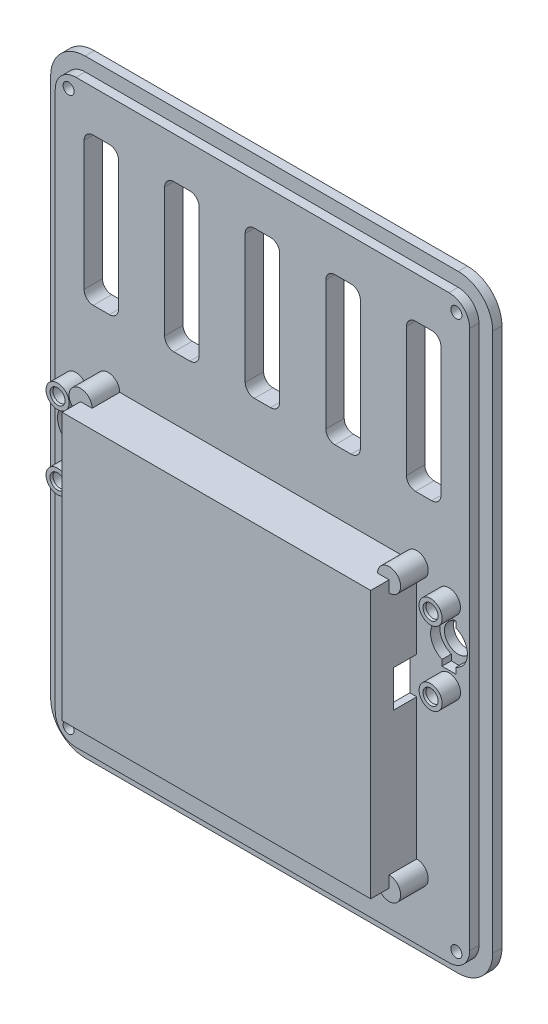
SolidWorks part; units mm, degrees
ref_plane "Front Plane" through (0, 0, 0) normal (0, 0, 1) x (1, 0, 0)
ref_plane "Top Plane" through (0, 0, 0) normal (0, 1, 0) x (1, 0, 0)
ref_plane "Right Plane" through (0, 0, 0) normal (1, 0, 0) x (0, 0, -1)
sketch "Sketch2" plane through (0, 0, 0) normal (0, 0, 1) x (1, 0, 0)
  line L20 (45, -58.5) -> (45, 58.5)
  line L21 (-40.5, -63) -> (40.5, -63)
  line L22 (-45, 58.5) -> (-45, -58.5)
  line L23 (40.5, 63) -> (-40.5, 63)
  line L24 (45, -58.5) -> (45, 58.5)
  line L25 (-40.5, -63) -> (40.5, -63)
  line L26 (-45, 58.5) -> (-45, -58.5)
  line L27 (40.5, 63) -> (-40.5, 63)
  arc A24 (40.5, -63) -> (45, -58.5) centre (40.5, -58.5) ccw
  arc A25 (-45, -58.5) -> (-40.5, -63) centre (-40.5, -58.5) ccw
  arc A26 (-40.5, 63) -> (-45, 58.5) centre (-40.5, 58.5) ccw
  arc A27 (45, 58.5) -> (40.5, 63) centre (40.5, 58.5) ccw
  arc A28 (40.5, -63) -> (45, -58.5) centre (40.5, -58.5) ccw
  arc A29 (-45, -58.5) -> (-40.5, -63) centre (-40.5, -58.5) ccw
  arc A30 (-40.5, 63) -> (-45, 58.5) centre (-40.5, 58.5) ccw
  arc A31 (45, 58.5) -> (40.5, 63) centre (40.5, 58.5) ccw
  dimension "D1" = 3
extrude "Boss-Extrude1" add sketch "Sketch2" along normal blind 2
sketch "Sketch3" plane through (0, 0, 0) normal (0, 0, -1) x (-1, 0, 0)
  line L8 (-40.5, -66) -> (40.5, -66)
  line L9 (48, -58.5) -> (48, 58.5)
  line L10 (40.5, 66) -> (-40.5, 66)
  line L11 (-48, 58.5) -> (-48, -58.5)
  line L12 (-40.5, -66) -> (40.5, -66)
  line L13 (48, -58.5) -> (48, 58.5)
  line L14 (40.5, 66) -> (-40.5, 66)
  line L15 (-48, 58.5) -> (-48, -58.5)
  arc A8 (-48, -58.5) -> (-40.5, -66) centre (-40.5, -58.5) ccw
  arc A9 (40.5, -66) -> (48, -58.5) centre (40.5, -58.5) ccw
  arc A10 (48, 58.5) -> (40.5, 66) centre (40.5, 58.5) ccw
  arc A11 (-40.5, 66) -> (-48, 58.5) centre (-40.5, 58.5) ccw
  arc A12 (-48, -58.5) -> (-40.5, -66) centre (-40.5, -58.5) ccw
  arc A13 (40.5, -66) -> (48, -58.5) centre (40.5, -58.5) ccw
  arc A14 (48, 58.5) -> (40.5, 66) centre (40.5, 58.5) ccw
  arc A15 (-40.5, 66) -> (-48, 58.5) centre (-40.5, 58.5) ccw
  dimension "D1" = 3
extrude "Boss-Extrude2" add sketch "Sketch3" along normal blind 2
sketch "Sketch5" plane through (0, 0, -2) normal (0, 0, -1) x (-1, 0, 0)
  line L0 (-48, 38) -> (48, 38) construction
  line L1 (-36.75, 22) -> (-33.25, 22)
  line L2 (-38.75, 24) -> (-38.75, 52)
  line L3 (-36.75, 54) -> (-33.25, 54)
  line L4 (-31.25, 24) -> (-31.25, 52)
  line L5 (-38.75, 22) -> (-31.25, 54) construction
  line L6 (-38.75, 54) -> (-31.25, 22) construction
  line L7 (-48, 58.5) -> (-48, -58.5) construction
  line L8 (48, -58.5) -> (48, 58.5) construction
  line L9 (40.5, 66) -> (-40.5, 66) construction
  line L10 (-21.25, 24) -> (-21.25, 52)
  line L11 (-13.75, 24) -> (-13.75, 52)
  line L12 (-19.25, 54) -> (-15.75, 54)
  line L13 (-19.25, 22) -> (-15.75, 22)
  line L14 (-21.25, 54) -> (-13.75, 22) construction
  line L15 (-21.25, 22) -> (-13.75, 54) construction
  line L16 (-3.75, 24) -> (-3.75, 52)
  line L17 (3.75, 24) -> (3.75, 52)
  line L18 (-1.75, 54) -> (1.75, 54)
  line L19 (-1.75, 22) -> (1.75, 22)
  line L20 (-3.75, 54) -> (3.75, 22) construction
  line L21 (-3.75, 22) -> (3.75, 54) construction
  line L22 (13.75, 24) -> (13.75, 52)
  line L23 (21.25, 24) -> (21.25, 52)
  line L24 (15.75, 54) -> (19.25, 54)
  line L25 (15.75, 22) -> (19.25, 22)
  line L26 (13.75, 54) -> (21.25, 22) construction
  line L27 (13.75, 22) -> (21.25, 54) construction
  line L28 (31.25, 24) -> (31.25, 52)
  line L29 (38.75, 24) -> (38.75, 52)
  line L30 (33.25, 54) -> (36.75, 54)
  line L31 (33.25, 22) -> (36.75, 22)
  line L32 (31.25, 54) -> (38.75, 22) construction
  line L33 (31.25, 22) -> (38.75, 54) construction
  line L34 (-3.5, 66) -> (-3.5, 34) construction
  arc A0 (31.25, 52) -> (33.25, 54) centre (33.25, 52) cw
  arc A1 (38.75, 52) -> (36.75, 54) centre (36.75, 52) ccw
  arc A2 (38.75, 24) -> (36.75, 22) centre (36.75, 24) cw
  arc A3 (31.25, 24) -> (33.25, 22) centre (33.25, 24) ccw
  arc A4 (13.75, 24) -> (15.75, 22) centre (15.75, 24) ccw
  arc A5 (21.25, 24) -> (19.25, 22) centre (19.25, 24) cw
  arc A6 (21.25, 52) -> (19.25, 54) centre (19.25, 52) ccw
  arc A7 (13.75, 52) -> (15.75, 54) centre (15.75, 52) cw
  arc A8 (3.75, 24) -> (1.75, 22) centre (1.75, 24) cw
  arc A9 (-3.75, 24) -> (-1.75, 22) centre (-1.75, 24) ccw
  arc A10 (3.75, 52) -> (1.75, 54) centre (1.75, 52) ccw
  arc A11 (-3.75, 52) -> (-1.75, 54) centre (-1.75, 52) cw
  arc A12 (-21.25, 24) -> (-19.25, 22) centre (-19.25, 24) ccw
  arc A13 (-13.75, 24) -> (-15.75, 22) centre (-15.75, 24) cw
  arc A14 (-13.75, 52) -> (-15.75, 54) centre (-15.75, 52) ccw
  arc A15 (-21.25, 52) -> (-19.25, 54) centre (-19.25, 52) cw
  arc A16 (-33.25, 22) -> (-31.25, 24) centre (-33.25, 24) ccw
  arc A17 (-36.75, 22) -> (-38.75, 24) centre (-36.75, 24) cw
  arc A18 (-33.25, 54) -> (-31.25, 52) centre (-33.25, 52) cw
  arc A19 (-38.75, 52) -> (-36.75, 54) centre (-36.75, 52) cw
  point P0 (-35, 38)
  point P13 (-17.5, 38)
  point P19 (0, 38)
  point P24 (17.5, 38)
  point P29 (35, 38)
  dimension "D6" = 2
  dimension "D1" = 7.5
  dimension "D2" = 32
  dimension "D3" = 28
  dimension "D5" = 10
  dimension "D4" = 5
extrude "Cut-Extrude1" cut sketch "Sketch5" against normal through all
hole_wizard "CBORE for M2 Pan Head Machine Screw1" positions "Sketch7" profile "Sketch6" counterbore size "M2" standard "ANSI Metric" end condition through all
sketch "Sketch7" plane through (0, 0, -2) normal (0, 0, -1) x (-1, 0, 0)
  point P0 (-42.1, 60.1)
  point P3 (42.1, 60.1)
  point P6 (-42.1, -60.1)
  point P9 (42.1, -60.1)
sketch "Sketch6" plane through (42.1, 60.1, -2) normal (1, 0, 0) x (0, 1, 0)
  line L0 (0, 0) -> (0, 4)
  line L1 (0, 4) -> (1.2, 4)
  line L3 (1.2, 4) -> (1.2, 1.6)
  line L4 (1.2, 1.6) -> (2.5, 1.6)
  line L5 (2.5, 1.6) -> (2.5, 0)
  line L7 (2.5, 0) -> (0, 0)
  line L11 (0, -6.35) -> (0, 107.95) construction
  dimension "Thru Hole Dia." = 2.4
  dimension "Thru Hole Depth" = 4
  dimension "C'Bore Dia." = 5
  dimension "C'Bore Depth" = 1.6
sketch "Sketch8" plane through (0, 0, -2) normal (0, 0, -1) x (-1, 0, 0)
  line L0 (0, 66) -> (0, -66) construction
  line L1 (-32, 7) -> (32, 7)
  line L2 (-32, 7) -> (-32, -48)
  line L3 (-32, -48) -> (32, -48)
  line L4 (32, 7) -> (32, -48)
  line L5 (-32, 7) -> (32, -48) construction
  line L6 (-32, -48) -> (32, 7) construction
  line L7 (40.5, 66) -> (-40.5, 66) construction
  line L8 (-40.5, -66) -> (40.5, -66) construction
  line L9 (-33.5, 8.5) -> (33.5, 8.5)
  line L10 (33.5, 8.5) -> (33.5, -49.5)
  line L11 (-33.5, -49.5) -> (33.5, -49.5)
  line L12 (-33.5, 8.5) -> (-33.5, -49.5)
  point P0 (0, -20.5)
  dimension "D1" = 18
  dimension "D2" = 55
  dimension "D3" = 64
  dimension "D4" = 1.5
extrude "Boss-Extrude3" add sketch "Sketch8<3>" against normal blind 10 from surface contours L9 L10 L11 L12 starting at face at (40.9, 60.1, 2)
sketch "Sketch8<3>" plane through (0, 0, -2) normal (0, 0, -1) x (-1, 0, 0) same geometry as "Sketch8"
extrude "Cut-Extrude2" cut sketch "Sketch8" against normal blind 12 contours L1 L4 L3 L2
sketch "Sketch9" plane through (0, 0, -2) normal (0, 0, -1) x (-1, 0, 0)
  line L18 (-36, -52) -> (36, -52)
  line L19 (36, -52) -> (36, 11)
  line L20 (-36, 11) -> (-36, -52)
  line L21 (36, 11) -> (-36, 11)
  line L22 (-36, -52) -> (36, -52)
  line L23 (36, -52) -> (36, 11)
  line L24 (-36, 11) -> (-36, -52)
  line L25 (36, 11) -> (-36, 11)
  dimension "D1" = 4
extrude "Cut-Extrude3" cut sketch "Sketch9" against normal blind 2
sketch "Sketch10" plane through (0, 0, 2) normal (0, 0, 1) x (1, 0, 0)
  line L0 (32, 7) -> (31.5, 7)
  line L1 (-32, 7) -> (-32, 6.5)
  line L2 (-32, -48) -> (-31.5, -48)
  line L3 (32, -48) -> (32, -47.5)
  line L4 (32, 6.5) -> (32, 7)
  line L5 (-31.5, 7) -> (-32, 7)
  line L6 (-32, -47.5) -> (-32, -48)
  line L7 (31.5, -48) -> (32, -48)
  arc A0 (32, 6.5) -> (31.5, 7) centre (33.5, 8.5) ccw
  arc A1 (-31.5, 7) -> (-32, 6.5) centre (-33.5, 8.5) ccw
  arc A2 (-32, -47.5) -> (-31.5, -48) centre (-33.5, -49.5) ccw
  arc A3 (31.5, -48) -> (32, -47.5) centre (33.5, -49.5) ccw
  dimension "D1" = 5
extrude "Boss-Extrude4" add sketch "Sketch10" along normal blind 6
hole_wizard "CSK for M2 Flat Head Machine Screw2" positions "Sketch14" profile "Sketch13" countersink size "M2" standard "ANSI Metric"
sketch "Sketch14" plane through (0, 0, 0) normal (0, 0, -1) x (-1, 0, 0)
  point P0 (-33.5, 8.5)
  point P3 (33.5, 8.5)
  point P6 (-33.5, -49.5)
  point P9 (33.5, -49.5)
sketch "Sketch13" plane through (33.5, 8.5, 0) normal (1, 0, 0) x (0, 1, 0)
  line L0 (0, 0) -> (0, 6.9013)
  line L1 (0, 6.9013) -> (1.5, 6)
  line L2 (1.5, 6) -> (1.5, 0.5038)
  line L3 (1.5, 0.5038) -> (1.635, 0)
  line L5 (1.635, 0) -> (0, 0)
  line L6 (-1.5, 0.5038) -> (-1.635, 0) construction
  line L10 (0, 6.9013) -> (-1.5, 6) construction
  line L11 (0, -6.35) -> (0, 107.95) construction
  dimension "Hole Dia." = 3
  dimension "Hole Depth" = 6
  dimension "Near C'Sink Dia." = 3.27
  dimension "Near C'Sink Angle" = 30
  dimension "Drill Angle" = 118
sketch "Sketch15" plane through (33.5, 0, 0) normal (1, 0, 0) x (0, 0, -1)
  line L1 (-7, -8.5) -> (-2, -8.5)
  line L2 (-7, -8.5) -> (-7, -16.5)
  line L3 (-7, -16.5) -> (-2, -16.5)
  line L4 (-2, -8.5) -> (-2, -16.5)
  line L5 (-2, -58.5) -> (-2, 58.5) construction
  line L6 (-12, 8.5) -> (-8, 8.5) construction
  dimension "D1" = 8
  dimension "D2" = 5
  dimension "D3" = 17
extrude "Cut-Extrude4" cut sketch "Sketch15" against normal through all
sketch "Sketch16" plane through (0, 0, -2) normal (0, 0, -1) x (-1, 0, 0)
  line L0 (2.5158, -57.4) -> (-2.5158, -57.4)
  line L1 (-4, -54.9) -> (-4, -55.719)
  line L2 (3.5, -54.4) -> (-3.5, -54.4)
  line L3 (4, -54.9) -> (4, -55.719)
  line L4 (0, -54.4) -> (0, -57.4) construction
  line L5 (-3.8841, -56.0391) -> (-2.8999, -57.2201)
  line L6 (3.8841, -56.0391) -> (2.8999, -57.2201)
  line L7 (0, 66) -> (0, -66) construction
  line L8 (40.5, 66) -> (-40.5, 66) construction
  line L9 (-40.5, -66) -> (40.5, -66) construction
  line L10 (40.5, -63) -> (-40.5, -63) construction
  arc A0 (-4, -55.719) -> (-3.8841, -56.0391) centre (-3.5, -55.719) ccw
  arc A1 (-2.5158, -57.4) -> (-2.8999, -57.2201) centre (-2.5158, -56.9) cw
  arc A2 (2.5158, -57.4) -> (2.8999, -57.2201) centre (2.5158, -56.9) ccw
  arc A3 (4, -55.719) -> (3.8841, -56.0391) centre (3.5, -55.719) cw
  arc A4 (4, -54.9) -> (3.5, -54.4) centre (3.5, -54.9) ccw
  arc A5 (-3.5, -54.4) -> (-4, -54.9) centre (-3.5, -54.9) ccw
  point P7 (0, -55.9)
  point P19 (-4, -55.9)
  point P22 (-2.75, -57.4)
  point P25 (2.75, -57.4)
  point P30 (4, -54.4)
  point P33 (-4, -54.4)
  dimension "D6" = 0.5
  dimension "D1" = 8
  dimension "D2" = 5.5
  dimension "D3" = 3
  dimension "D4" = 1.5
  dimension "D5" = 5.6
extrude "Cut-Extrude5" cut sketch "Sketch16" against normal through all
sketch "Sketch17" plane through (0, 0, 0) normal (0, 0, -1) x (-1, 0, 0)
  line L0 (45, 58.5) -> (45, -58.5) construction
  line L1 (42, 0.7081) -> (42, 2)
  line L2 (-39, 0.7081) -> (-39, 2)
  line L3 (39, 0.7081) -> (39, 2)
  line L4 (40.5, -63) -> (-40.5, -63) construction
  line L5 (-39, -8) -> (-42, -8)
  line L6 (-45, -58.5) -> (-45, 58.5) construction
  line L7 (-39, -8) -> (-39, -6.7081)
  line L8 (40.5, -63) -> (-40.5, -63) construction
  line L9 (-39, 2) -> (-42, 2)
  line L10 (42, -8) -> (39, -8)
  line L11 (42, -8) -> (42, -6.7081)
  line L12 (42, 2) -> (39, 2)
  line L13 (39, -8) -> (39, -6.7081)
  line L14 (42, -8) -> (39, 2) construction
  line L15 (42, 2) -> (39, -8) construction
  line L16 (-42, -8) -> (-42, -6.7081)
  line L17 (-39, -8) -> (-42, 2) construction
  line L18 (-39, 2) -> (-42, -8) construction
  line L19 (-42, 0.7081) -> (-42, 2)
  circle A0 centre (40.5, -3) radius 3
  circle A1 centre (-40.5, -3) radius 3
  arc A2 (39, 0.7081) -> (39, -6.7081) centre (40.5, -3) ccw
  arc A3 (42, -6.7081) -> (42, 0.7081) centre (40.5, -3) ccw
  circle A4 centre (40.5, -3) radius 4 construction
  arc A5 (-42, 0.7081) -> (-42, -6.7081) centre (-40.5, -3) ccw
  arc A6 (-39, -6.7081) -> (-39, 0.7081) centre (-40.5, -3) ccw
  circle A7 centre (-40.5, -3) radius 4 construction
  point P9 (40.5, -3)
  point P18 (-40.5, -3)
  point P25 (44, -3)
  point P34 (-36, -3)
  dimension "D2" = 6
  dimension "D1" = 4.5
  dimension "D3" = 60
  dimension "D4" = 4.5
  dimension "D5" = 60
  dimension "D7" = 10
  dimension "D8" = 1
  dimension "D9" = 3
  dimension "D10" = 3
  dimension "D11" = 10
  dimension "D6" = 1
extrude "Cut-Extrude7" cut sketch "Sketch17" along normal up to surface (2 mm away) and the other way through all contours A0 | A1 up to face at (0, -55.9379, -2)
extrude "Cut-Extrude8" cut sketch "Sketch17<3>" along normal blind 2 from surface contours A2 L13 L10 L11 A3 L1 L12 L3 | A5 L16 L5 L7 A6 L2 L9 L19 starting at face at (43.5, -3, 2)
sketch "Sketch17<3>" plane through (0, 0, 0) normal (0, 0, -1) x (-1, 0, 0) same geometry as "Sketch17"
sketch "Sketch18" plane through (0, 0, 2) normal (0, 0, 1) x (1, 0, 0)
  line L0 (-40.5, 5) -> (-40.5, -11) construction
  line L1 (-40.5, 5) -> (40.5, 5) construction
  line L2 (-40.5, -11) -> (40.5, -11) construction
  line L3 (40.5, -11) -> (40.5, 5) construction
  circle A0 centre (-40.5, 5) radius 2.5
  circle A1 centre (-40.5, -11) radius 2.5
  circle A3 centre (40.5, 5) radius 2.5
  circle A4 centre (40.5, -11) radius 2.5
  point P5 (-40.5, -3)
  point P13 (40.5, -3)
  dimension "D1" = 5
  dimension "D2" = 16
  dimension "D3" = 8
extrude "Boss-Extrude5" add sketch "Sketch18" along normal blind 4
hole_wizard "CSK for M2 Flat Head Machine Screw4" positions "3DSketch2" profile "Sketch20" countersink size "M2" standard "ANSI Metric"
sketch3d "3DSketch2"
  line L0 (40.5, 5, 6) -> (40.5, 5, 2) construction
  line L1 (40.5, -11, 6) -> (40.5, -11, 2) construction
  line L2 (-40.5, 5, 6) -> (-40.5, 5, 2) construction
  line L3 (-40.5, -11, 6) -> (-40.5, -11, 2) construction
  point P0 (40.5, 5, 6)
  point P4 (40.5, -11, 6)
  point P8 (-40.5, 5, 6)
  point P12 (-40.5, -11, 6)
sketch "Sketch20" plane through (40.5, 5, 6) normal (1, 0, 0) x (0, -1, 0)
  line L0 (0, 0) -> (0, 6)
  line L1 (0, 6) -> (1.5, 6)
  line L2 (1.5, 6) -> (1.5, 0.5038)
  line L3 (1.5, 0.5038) -> (1.635, 0)
  line L5 (1.635, 0) -> (0, 0)
  line L6 (-1.5, 0.5038) -> (-1.635, 0) construction
  line L10 (0, 6) -> (-1.5, 6) construction
  line L11 (0, -6.35) -> (0, 107.95) construction
  dimension "Hole Dia." = 3
  dimension "Hole Depth" = 6
  dimension "Near C'Sink Dia." = 3.27
  dimension "Near C'Sink Angle" = 30
  dimension "Drill Angle" = 180
